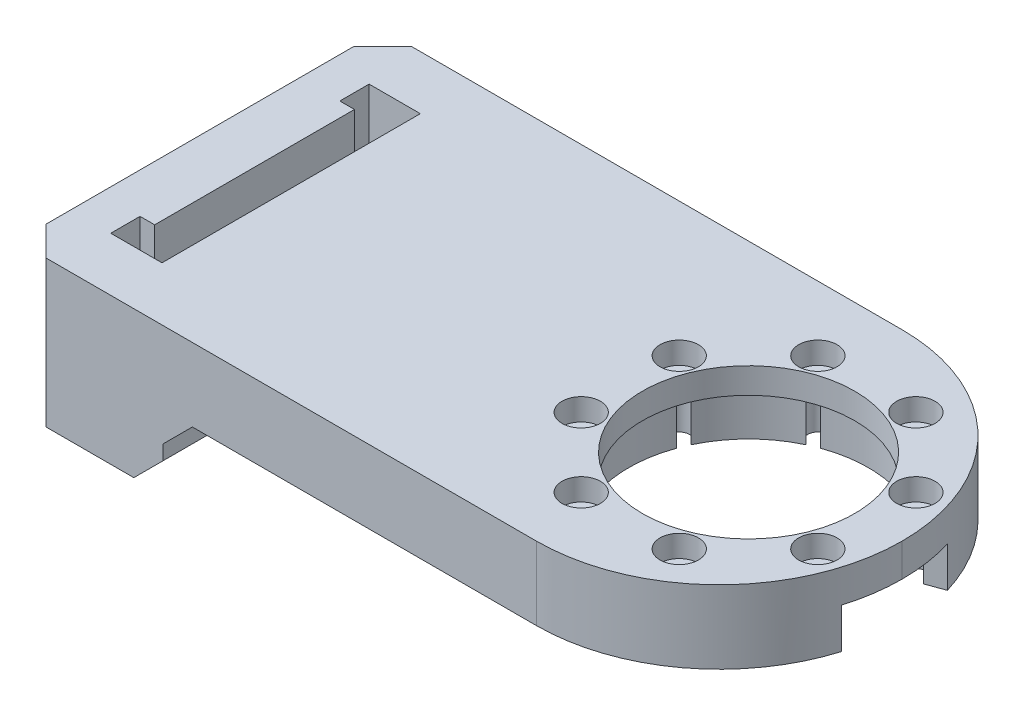
SolidWorks part; units mm, degrees
ref_plane "Front Plane" through (0, 0, 0) normal (0, 0, 1) x (1, 0, 0)
ref_plane "Top Plane" through (0, 0, 0) normal (0, 1, 0) x (1, 0, 0)
ref_plane "Right Plane" through (0, 0, 0) normal (1, 0, 0) x (0, 0, -1)
sketch "Sketch1" plane through (0, 0, 0) normal (0, 1, 0) x (1, 0, 0)
  line L0 (-122.4227, 0) -> (145.8763, 0) construction
  line L1 (-110, -50) -> (42, -50)
  line L2 (-110, -50) -> (-110, 50)
  line L3 (-110, 50) -> (42, 50)
  line L4 (42, -50) -> (42, 50)
  line L5 (0, 66.7862) -> (0, -70.0911) construction
  point P0 (0, 0)
  point P8 (-42.5, 0)
  point P11 (-110, 0)
  dimension "D1" = 100
  dimension "D2" = 110
  dimension "D3" = 42
extrude "Boss-Extrude1" add sketch "Sketch1" along normal blind 20
sketch "Sketch18" plane through (0, 0, 0) normal (0, 1, 0) x (1, 0, 0)
  line L0 (42, 50) -> (-110, 50) construction
  line L1 (-110, -50) -> (-150, -50)
  line L2 (-110, -50) -> (-110, 50)
  line L3 (-110, 50) -> (-150, 50)
  line L4 (-150, -50) -> (-150, 50)
  line L5 (58.2373, 0) -> (-183.2756, 0) construction
  line L7 (-135, -35.3) -> (-125, -35.3)
  line L8 (-135, -35.3) -> (-135, 35.3)
  line L9 (-135, 35.3) -> (-125, 35.3)
  line L10 (-125, -35.3) -> (-125, 35.3)
  line L11 (-135, -35.3) -> (-125, 35.3) construction
  line L12 (-135, 35.3) -> (-125, -35.3) construction
  point P10 (-130, 0)
  dimension "D1" = 40
  dimension "D2" = 10
  dimension "D3" = 70.6
  dimension "D4" = 15
extrude "Boss-Extrude2" add sketch "Sketch18" along normal up to surface (20 mm away) and the other way blind 20 up to face at (-34, 20, 0)
sketch "Sketch19" plane through (0, 0, 0) normal (0, 1, 0) x (1, 0, 0)
  line L0 (-179.1166, 0) -> (58.3774, 0) construction
  line L1 (-139, -35.3) -> (-139, -27.3)
  line L2 (-135, 35.3) -> (-139, 35.3)
  line L3 (-135, 35.3) -> (-135, 27.3)
  line L4 (-135, 27.3) -> (-139, 27.3)
  line L5 (-139, 35.3) -> (-139, 27.3)
  line L6 (-135, -27.3) -> (-139, -27.3)
  line L7 (-135, -35.3) -> (-135, -27.3)
  line L8 (-135, -35.3) -> (-139, -35.3)
  dimension "D1" = 8
  dimension "D2" = 4
extrude "Cut-Extrude3" cut sketch "Sketch19" against normal through all both and the other way through all
sketch "Sketch20" plane through (-150, 0, 0) normal (-1, 0, 0) x (0, 0, 1)
  line L0 (0, 26.3744) -> (0, -25.743) construction
  line L1 (-27.3, 0) -> (-35.3, 0) construction
  line L2 (-27.3, -20) -> (-27.3, 20) construction
  line L3 (-35.3, -20) -> (-35.3, 20) construction
  circle A0 centre (-31.3, 0) radius 2.5
  circle A1 centre (31.3, 0) radius 2.5
  dimension "D1" = 5
extrude "Cut-Extrude4" cut sketch "Sketch20" against normal blind 15
chamfer "Chamfer1" distance 8 angle 45 4 edges at (-150, 0, -50) (-150, 0, 50) (-110, -20, 0) (-110, 0, 0)
sketch "Sketch11" plane through (0, 20, 0) normal (0, 1, 0) x (1, 0, 0)
  line L0 (-101.1107, 0) -> (116.3501, 0) construction
  line L1 (0, 67.1499) -> (0, -68.5966) construction
  line L2 (0, 0) -> (-13.2056, -5.4699) construction
  circle A0 centre (0, 0) radius 35 construction
  circle A1 centre (0, 0) radius 29
  point P8 (-32.3358, -13.3939)
  point P10 (-32.3358, 13.3939)
  point P11 (0, 0)
  point P12 (-13.3939, 32.3358)
  point P24 (0, 0)
  point P25 (13.3939, 32.3358)
  point P26 (32.3358, 13.3939)
  point P27 (32.3358, -13.3939)
  point P28 (13.3939, -32.3358)
  point P29 (-13.3939, -32.3358)
  dimension "D1" = 70
  dimension "D5" = 58
  dimension "D3" = 22.5
  dimension "D2" = 8
extrude "Cut-Extrude1" cut sketch "Sketch11" against normal through all both and the other way through all
sketch "Sketch21" plane through (0, 0, 0) normal (0, 1, 0) x (1, 0, 0)
  line L0 (0, 0) -> (52.8665, -19.2418)
  line L1 (0, 0) -> (59.9919, 0) construction
  line L2 (0, 0) -> (52.8665, 19.2418)
  line L3 (52.8665, -19.2418) -> (52.8665, 19.2418)
  dimension "D1" = 40
extrude "Cut-Extrude5" cut sketch "Sketch21" along normal blind 11
sketch "Sketch15" plane through (0, 0, 0) normal (0, 1, 0) x (1, 0, 0)
  circle A0 centre (0, 0) radius 32.75
  dimension "D1" = 65.5
extrude "Cut-Extrude2" cut sketch "Sketch15" along normal blind 13
hole_wizard "CBORE for M5 Hex Head Bolt2" positions "3DSketch11" profile "Sketch14" counterbore size "M5" standard "BSI" end condition through all
sketch3d "3DSketch11"
  point P0 (-32.3358, 20, -13.3939)
  point P3 (-13.3939, 20, -32.3358)
  point P6 (13.3939, 20, -32.3358)
  point P9 (32.3358, 20, -13.3939)
  point P12 (32.3358, 20, 13.3939)
  point P15 (13.3939, 20, 32.3358)
  point P18 (-13.3939, 20, 32.3358)
  point P21 (-32.3358, 20, 13.3939)
sketch "Sketch14" plane through (-32.3358, 20, -13.3939) normal (1, 0, 0) x (0, 0, 1)
  line L0 (0, 0) -> (0, 40)
  line L1 (0, 40) -> (2.75, 40)
  line L3 (2.75, 40) -> (2.75, 6)
  line L4 (2.75, 6) -> (5.25, 6)
  line L5 (5.25, 6) -> (5.25, 0)
  line L7 (5.25, 0) -> (0, 0)
  line L11 (0, -6.35) -> (0, 107.95) construction
  dimension "Thru Hole Dia." = 5.5
  dimension "Thru Hole Depth" = 40
  dimension "C'Bore Dia." = 10.5
  dimension "C'Bore Depth" = 6
sketch "Sketch22" [suppressed] plane through (0, 0, 0) normal (0, 1, 0) x (1, 0, 0)
  circle A0 centre (0, 0) radius 27.6
  dimension "D1" = 55.2
extrude "Cut-Extrude6" [suppressed] cut sketch "Sketch22" along normal blind 13.5
sketch "Sketch24" [suppressed] plane through (0, 0, 0) normal (0, 1, 0) x (1, 0, 0)
  circle A2 centre (0, 0) radius 22.6
  circle A3 centre (0, 0) radius 22.6
  dimension "D1" = 5
extrude "Cut-Extrude7" [suppressed] cut sketch "Sketch24" along normal through all
sketch "Sketch25" [suppressed] plane through (0, 0, 0) normal (0, 1, 0) x (1, 0, 0)
  line L0 (77.8283, 0) -> (-47.1121, 0) construction
  line L2 (0, -1.25) -> (60, -1.25)
  line L3 (0, -1.25) -> (0, 1.25)
  line L4 (0, 1.25) -> (60, 1.25)
  line L5 (60, -1.25) -> (60, 1.25)
  line L6 (0, -1.25) -> (60, 1.25) construction
  line L7 (0, 1.25) -> (60, -1.25) construction
  point P2 (30, 0)
  dimension "D1" = 2.5
  dimension "D2" = 60
extrude "Cut-Extrude9" [suppressed] cut sketch "Sketch25" against normal through all both and the other way through all
sketch "Sketch26" [suppressed] plane through (40, 0, 0) normal (1, 0, 0) x (0, 0, -1)
  line L0 (-11.25, 20) -> (-11.25, 0) construction
  line L1 (-50, 20) -> (-1.25, 20) construction
  line L2 (-50, 0) -> (-1.25, 0) construction
  line L3 (-50, 10) -> (-1.25, 10) construction
  line L4 (-50, 20) -> (-50, 0) construction
  line L5 (-1.25, 0) -> (-1.25, 13.5) construction
  line L6 (-1.25, 0) -> (-1.25, 20) construction
  line L7 (-13.25, 14) -> (-9.25, 14)
  line L8 (-13.25, 14) -> (-13.25, 6)
  line L9 (-13.25, 6) -> (-9.25, 6)
  line L10 (-9.25, 14) -> (-9.25, 6)
  line L11 (-13.25, 14) -> (-9.25, 6) construction
  line L12 (-13.25, 6) -> (-9.25, 14) construction
  point P12 (-11.25, 10)
  point P13 (-11.25, 10)
  dimension "D1" = 8
  dimension "D2" = 4
  dimension "D3" = 10
extrude "Cut-Extrude10" [suppressed] cut sketch "Sketch26" against normal blind 29
sketch "Sketch27" [suppressed] plane through (0, 0, -50) normal (0, 0, -1) x (-1, 0, 0)
  line L0 (-33, 20) -> (-33, 0) construction
  line L1 (-40, 20) -> (142, 20) construction
  line L2 (-40, 0) -> (102, 0) construction
  line L3 (-40, 10) -> (-8.6813, 10) construction
  line L4 (-40, 20) -> (-40, 0) construction
  circle A0 centre (-33, 10) radius 2.75
  dimension "D2" = 5.5
  dimension "D1" = 7
extrude "Cut-Extrude11" [suppressed] cut sketch "Sketch27" against normal through all
sketch "Sketch28" [suppressed] plane through (0, 0, -50) normal (0, 0, -1) x (-1, 0, 0)
  circle A0 centre (-33, 10) radius 5
  dimension "D1" = 10
extrude "Cut-Extrude12" [suppressed] cut sketch "Sketch28" against normal offset from surface (38.75 mm away) 10
fillet "Fillet1" radius 50 2 edges at (42, 10, -50) (42, 10, 50)
sketch "Sketch29" [suppressed] plane through (0, 0, 0) normal (0, 1, 0) x (1, 0, 0)
  line L0 (-173.7828, 0) -> (83.0474, 0) construction
  circle A0 centre (0, 0) radius 75 construction
  circle A1 centre (-75, 0) radius 2.75
  circle A2 centre (-71.7983, 21.6796) radius 2.75
  circle A3 centre (-71.5859, -22.3708) radius 2.75
  dimension "D1" = 150
  dimension "D2" = 5.5
extrude "Cut-Extrude13" [suppressed] cut sketch "Sketch29" along normal through all
